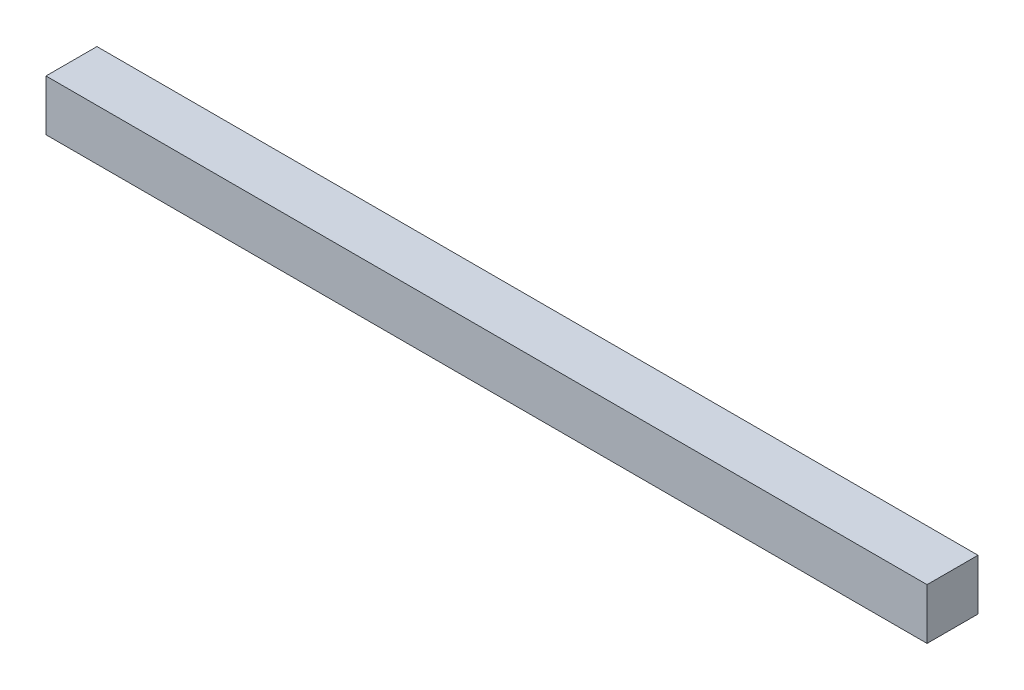
SolidWorks part; units mm, degrees
ref_plane "Plan de face" through (0, 0, 0) normal (0, 0, 1) x (1, 0, 0)
ref_plane "Plan de dessus" through (0, 0, 0) normal (0, 1, 0) x (1, 0, 0)
ref_plane "Plan de droite" through (0, 0, 0) normal (1, 0, 0) x (0, 0, -1)
sketch "Esquisse1" plane through (0, 0, 0) normal (0, 0, 1) x (1, 0, 0)
  line L1 (-87.5927, 45.5455) -> (85.4073, 45.5455)
  line L2 (-87.5927, 45.5455) -> (-87.5927, 35.5455)
  line L3 (-87.5927, 35.5455) -> (85.4073, 35.5455)
  line L4 (85.4073, 45.5455) -> (85.4073, 35.5455)
  dimension "D1" = 10
  dimension "D2" = 173
extrude "Boss.-Extru.1" add sketch "Esquisse1" along normal blind 10
equation "\"EpaisseurPlaque\"= 3"
equation "\"ProfondeurBoite\"=460"
equation "\"LongueurSyphon\"=170"
equation "\"LargeurSyphon\"=120"
equation "\"HauteurCoteDroit\"= 490"
equation "\"HauteurCoteGauche\"= 540"
equation "\"HauteurSolSyphon\"= 300"
equation "\"HauteurSyphon\"=\"HauteurCoteGauche\"-\"HauteurSolSyphon\""
equation "\"LargeurDroite\"=10"
equation "\"LargeurGauche\"=150"
equation "\"LargeurBoite\"= \"LargeurDroite\" + \"LargeurGauche\" + \"LargeurSyphon\""
equation "\"D2@Esquisse1\"=\"LongueurSyphon\" + 3"
